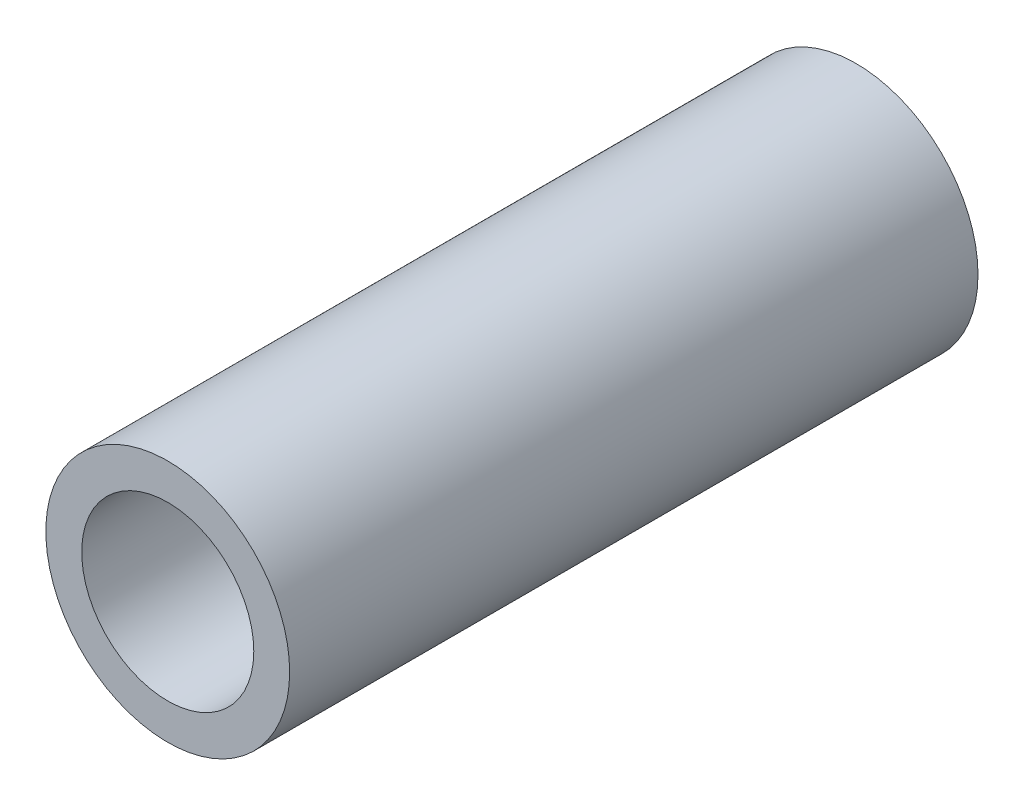
SolidWorks part; units mm, degrees
material "Silicon Rubber"
ref_plane "X-Y Datum" through (0, 0, 0) normal (0, 0, 1) x (1, 0, 0)
ref_plane "X-Z Datum" through (0, 0, 0) normal (0, 1, 0) x (1, 0, 0)
ref_plane "Y-Z Datum" through (0, 0, 0) normal (1, 0, 0) x (0, 0, -1)
sketch3d "3DSketch1"
  line L0 (0, 0, 0) -> (0, 0, 76.2)
  dimension "D1" = 76.2
sweep "Sweep1" add path "3DSketch1" circular profile diameter 26.9875 parameters "D3"=26.9875
sweep "Cut-Sweep1" cut path "3DSketch1<2>" circular profile diameter 19.05 parameters "D3"=19.05
sketch3d "3DSketch1<2>" same geometry as "3DSketch1"
sketch3d "3DSketch2"
  circle A0 centre (0, 0, 50.8) radius 9.525 construction
  circle A1 centre (0, 0, 25.4) radius 9.525 construction
  circle A2 centre (0, 0, 76.2) radius 13.4937 construction
  circle A5 centre (0, 0, 0) radius 9.525 construction
  point P4 (0, 0, 15.875)
  point P5 (0, 0, -9.525)
  point P8 (0, 0, 41.275)
  point P9 (-18.2819, 10.9761, 55.7563)
  point P12 (0, 0, 89.6937)
  dimension "D1" = 25.4
  dimension "D2" = 25.4
